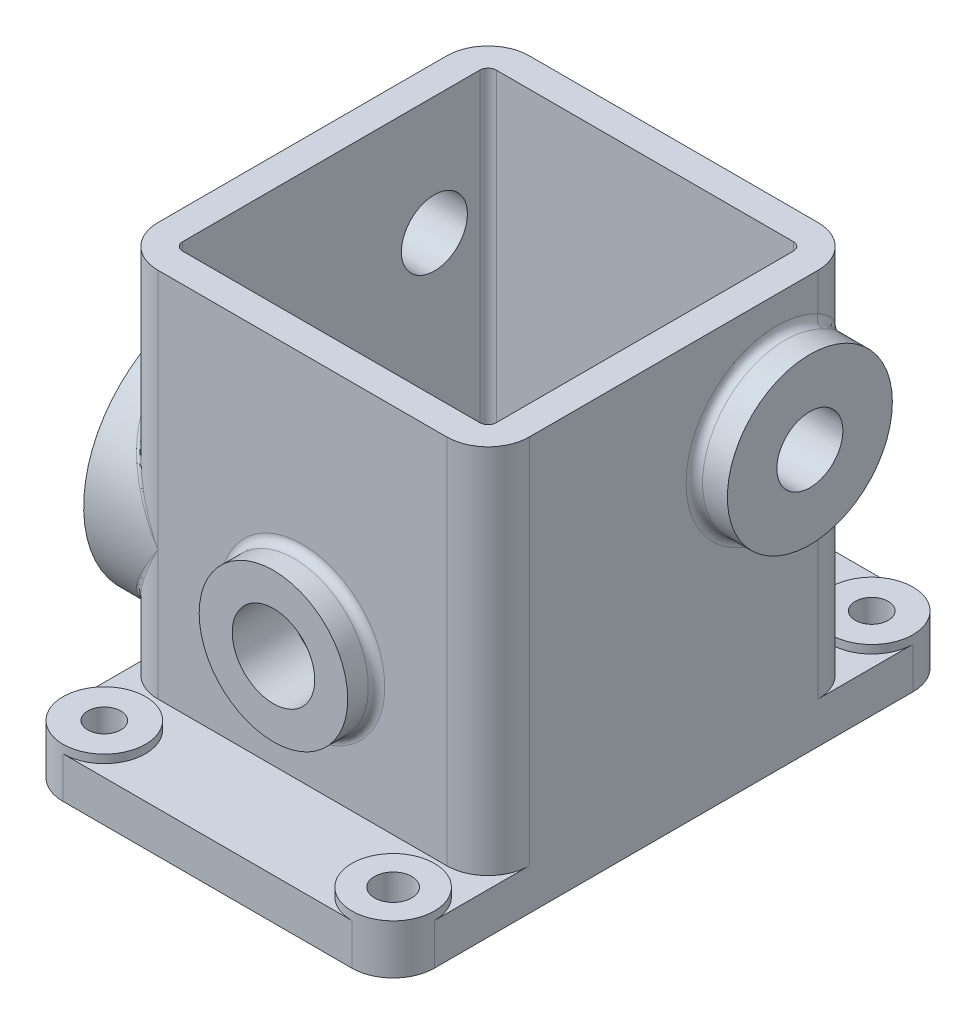
SolidWorks part; units mm, degrees
ref_plane "前视基准面" through (0, 0, 0) normal (0, 0, 1) x (1, 0, 0)
ref_plane "上视基准面" through (0, 0, 0) normal (0, 1, 0) x (1, 0, 0)
ref_plane "右视基准面" through (0, 0, 0) normal (1, 0, 0) x (0, 0, -1)
sketch "草图1" plane through (0, 0, 0) normal (0, 1, 0) x (1, 0, 0)
  line L0 (0, 0) -> (0, 136)
  line L1 (0, 136) -> (90, 136)
  line L2 (90, 136) -> (90, 0)
  line L3 (90, 0) -> (0, 0)
  dimension "D1" = 136
  dimension "D2" = 90
extrude "凸台-拉伸1" add sketch "草图1" along normal blind 10
fillet "圆角1" radius 10 4 edges at (90, 5, -136) (0, 5, -136) (0, 5, 0) (90, 5, 0)
sketch "草图2" plane through (0, 10, 0) normal (0, 1, 0) x (1, 0, 0)
  line L0 (-17.6553, 68) -> (125.5944, 68) construction
  line L1 (45, -10.352) -> (45, 140.812) construction
  line L2 (0, 33) -> (0, 103)
  line L3 (0, 126) -> (0, 10) construction
  line L4 (10, 113) -> (80, 113)
  line L5 (90, 10) -> (90, 126) construction
  line L6 (90, 103) -> (90, 33)
  line L7 (80, 23) -> (10, 23)
  line L8 (80, 136) -> (10, 136) construction
  arc A0 (0, 33) -> (10, 23) centre (10, 33) ccw
  arc A1 (80, 23) -> (90, 33) centre (80, 33) ccw
  arc A2 (90, 103) -> (80, 113) centre (80, 103) ccw
  arc A3 (0, 103) -> (10, 113) centre (10, 103) cw
  point P17 (0, 23)
  point P20 (90, 23)
  point P23 (90, 113)
  point P26 (0, 113)
  dimension "D3" = 10
  dimension "D1" = 90
  dimension "D2" = 68
extrude "凸台-拉伸2" add sketch "草图2" along normal blind 90
sketch "草图3" plane through (0, 100, 0) normal (0, 1, 0) x (1, 0, 0)
  line L0 (80, 113) -> (10, 113) construction
  line L1 (9, 30) -> (81, 30)
  line L2 (7, 32) -> (7, 104)
  line L3 (9, 106) -> (81, 106)
  line L4 (83, 32) -> (83, 104)
  line L5 (0, 103) -> (0, 33) construction
  arc A0 (9, 30) -> (7, 32) centre (9, 32) cw
  arc A1 (81, 30) -> (83, 32) centre (81, 32) ccw
  arc A2 (81, 106) -> (83, 104) centre (81, 104) cw
  arc A3 (7, 104) -> (9, 106) centre (9, 104) cw
  point P10 (7, 30)
  point P15 (83, 106)
  point P18 (7, 106)
  dimension "D5" = 2
  dimension "D1" = 76
  dimension "D2" = 7
  dimension "D3" = 76
  dimension "D4" = 7
extrude "切除-拉伸1" cut sketch "草图3" against normal through all
sketch "草图4" plane through (0, 10, 0) normal (0, 1, 0) x (1, 0, 0)
  circle A0 centre (10, 126) radius 10
  circle A1 centre (80, 126) radius 10
  circle A2 centre (80, 10) radius 10
  circle A3 centre (10, 10) radius 10
  dimension "D1" = 20
extrude "凸台-拉伸3" add sketch "草图4" along normal blind 2
sketch "草图5" plane through (0, 12, 0) normal (0, 1, 0) x (1, 0, 0)
  circle A0 centre (10, 126) radius 4
  circle A1 centre (80, 126) radius 4
  circle A2 centre (80, 10) radius 4.5222
  circle A3 centre (10, 10) radius 4
  dimension "D1" = 8
extrude "切除-拉伸2" cut sketch "草图5" against normal through all
ref_plane "基准面1" through (-8, 0, 0) normal (-1, 0, 0) x (0, 0, 1)
sketch "草图6" plane through (-8, 0, 0) normal (-1, 0, 0) x (0, 0, 1)
  line L0 (-113, 100) -> (-113, 10) construction
  arc A0 (-73.4405, 75.5123) -> (-91.5309, 51.3917) centre (-93, 71.3377) ccw
  arc A1 (-82.9552, 42.9764) -> (-62.9606, 69.6359) centre (-53, 41.3377) ccw
  arc A2 (-82.9552, 42.9764) -> (-91.5309, 51.3917) centre (-90.9433, 43.4134) ccw
  arc A3 (-73.4405, 75.5123) -> (-62.9606, 69.6359) centre (-65.6167, 77.1821) ccw
  dimension "D1" = 40
  dimension "D2" = 60
  dimension "D5" = 16
  dimension "D6" = 16
  dimension "D3" = 40
  dimension "D4" = 30
extrude "凸台-拉伸4" add sketch "草图6" against normal up to body
fillet "圆角2" radius 2 10 edges at (3.274, 61.4767, -110.4) (0, 51.842, -97.4629) (0, 49.1233, -85.34) (3.4013, 29.3799, -25.4862) (3.4013, 53.2955, -25.4862) (0, 70.7654, -47.1681) (0, 70.2042, -69.5294) (3.274, 81.1987, -110.4) (0, 14.2964, -65.9911) (0, 89.612, -84.8729)
ref_plane "基准面2" through (98, 0, 0) normal (1, 0, 0) x (0, 0, -1)
sketch "草图9" plane through (98, 0, 0) normal (1, 0, 0) x (0, 0, -1)
  circle A0 centre (93, 71.3377) radius 20
  dimension "D1" = 40
extrude "凸台-拉伸5" add sketch "草图9" against normal up to body
fillet "圆角3" radius 2 3 edges at (86.726, 81.1987, -110.4) (86.726, 61.4767, -110.4) (90, 71.3377, -73)
sketch "草图10" plane through (98, 0, 0) normal (1, 0, 0) x (0, 0, -1)
  circle A0 centre (93, 71.3377) radius 8
  dimension "D1" = 16
extrude "切除-拉伸4" cut sketch "草图10" against normal through all
sketch "草图11" plane through (-8, 0, 0) normal (-1, 0, 0) x (0, 0, 1)
  circle A0 centre (-53, 41.3377) radius 16
  dimension "D1" = 32
extrude "切除-拉伸5" cut sketch "草图11" against normal blind 32
ref_plane "基准面3" through (0, 0, -68) normal (0, 0, 1) x (1, 0, 0)
sketch "草图12" plane through (0, 0, -23) normal (0, 0, 1) x (1, 0, 0)
  line L0 (80, 0) -> (10, 0) construction
  circle A0 centre (45, 40) radius 18
  point P2 (45, 0)
  dimension "D1" = 36
  dimension "D2" = 40
extrude "凸台-拉伸6" add sketch "草图12" along normal blind 7
sketch "草图14" plane through (0, 0, -16) normal (0, 0, 1) x (1, 0, 0)
  circle A0 centre (45, 40) radius 10
  dimension "D1" = 20
extrude "切除-拉伸6" cut sketch "草图14" against normal blind 27
fillet "圆角4" radius 2 1 edges at (27, 40, -23)
mirror "镜向3" about plane through (0, 0, -68) normal (0, 0, 1) of "切除-拉伸6", "凸台-拉伸6"
fillet "圆角5" radius 2 1 edges at (63, 40, -113)
